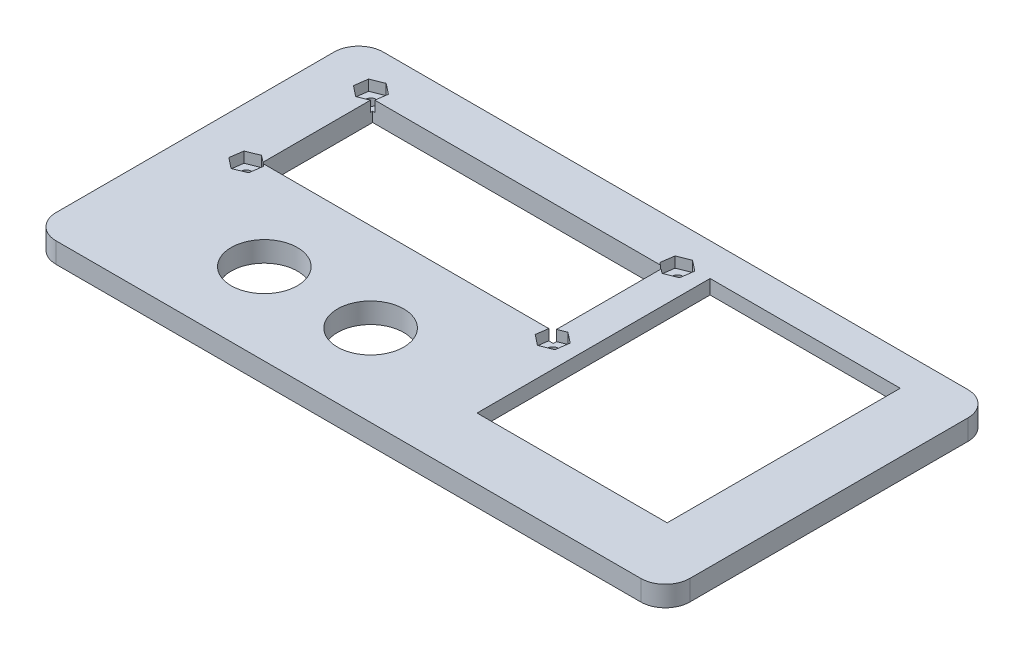
SolidWorks part; units mm, degrees
ref_plane "Front Plane" through (0, 0, 0) normal (0, 0, 1) x (1, 0, 0)
ref_plane "Top Plane" through (0, 0, 0) normal (0, 1, 0) x (1, 0, 0)
ref_plane "Right Plane" through (0, 0, 0) normal (1, 0, 0) x (0, 0, -1)
sketch "Sketch1" plane through (0, 0, 0) normal (0, 1, 0) x (1, 0, 0)
  line L1 (-77.5, -40) -> (77.5, -40)
  line L2 (-77.5, -40) -> (-77.5, 40)
  line L3 (-77.5, 40) -> (77.5, 40)
  line L4 (77.5, -40) -> (77.5, 40)
  line L5 (-77.5, -40) -> (77.5, 40) construction
  line L6 (-77.5, 40) -> (77.5, -40) construction
  point P0 (0, 0)
  dimension "D1" = 155
  dimension "D2" = 80
extrude "Boss-Extrude1" add sketch "Sketch1" along normal blind 5
sketch "Sketch2" plane through (0, 5, 0) normal (0, 1, 0) x (1, 0, 0)
  line L1 (-62.8518, 1.6691) -> (8.446, 1.6691)
  line L2 (-62.8518, 1.6691) -> (-62.8518, 28.7709)
  line L3 (-62.8518, 28.7709) -> (8.446, 28.7709)
  line L4 (8.446, 1.6691) -> (8.446, 28.7709)
  line L5 (-62.8518, 1.6691) -> (8.446, 28.7709) construction
  line L6 (-62.8518, 28.7709) -> (8.446, 1.6691) construction
  line L7 (-67.5, 15.22) -> (12.51, 15.22) construction
  line L8 (-67.5, 33) -> (12.51, 33) construction
  line L9 (-67.5, 33) -> (-67.5, -2.56) construction
  line L10 (-67.5, -2.56) -> (12.51, -2.56) construction
  line L11 (12.51, 33) -> (12.51, -2.56) construction
  line L12 (77.5, 40) -> (-77.5, 40) construction
  line L13 (-77.5, 40) -> (-77.5, -40) construction
  circle A0 centre (-64.96, -0.02) radius 1.27
  circle A1 centre (9.97, -0.02) radius 1.27
  circle A2 centre (9.97, 30.46) radius 1.27
  circle A3 centre (-64.96, 30.46) radius 1.27
  point P0 (-27.2029, 15.22)
  point P6 (-27.2029, 17.22)
  point P20 (-27.495, 15.22)
  dimension "D7" = 2.54
  dimension "D8" = 2.54
  dimension "D1" = 71.2978
  dimension "D2" = 27.1018
  dimension "D3" = 7
  dimension "D4" = 35.56
  dimension "D5" = 80.01
  dimension "D6" = 4.6482
  dimension "D9" = 33.02
  dimension "D10" = 77.47
  dimension "D11" = 5.08
  dimension "D12" = 10
extrude "Screen Cutout" cut sketch "Sketch2" against normal through all
sketch "Sketch8" plane through (0, 5, 0) normal (0, 1, 0) x (1, 0, 0)
  line L1 (-68.0135, 29.2327) -> (-65.4238, 27.202)
  line L2 (-65.4238, 27.202) -> (-62.3704, 28.4293)
  line L3 (-62.3704, 28.4293) -> (-61.9065, 31.6873)
  line L4 (-61.9065, 31.6873) -> (-64.4962, 33.718)
  line L5 (-64.4962, 33.718) -> (-67.5496, 32.4907)
  line L6 (-67.5496, 32.4907) -> (-68.0135, 29.2327)
  line L7 (6.9165, 29.2327) -> (9.5062, 27.202)
  line L8 (9.5062, 27.202) -> (12.5596, 28.4293)
  line L9 (12.5596, 28.4293) -> (13.0235, 31.6873)
  line L10 (13.0235, 31.6873) -> (10.4338, 33.718)
  line L11 (10.4338, 33.718) -> (7.3804, 32.4907)
  line L12 (7.3804, 32.4907) -> (6.9165, 29.2327)
  line L13 (6.9165, -1.2473) -> (9.5062, -3.278)
  line L14 (9.5062, -3.278) -> (12.5596, -2.0507)
  line L15 (12.5596, -2.0507) -> (13.0235, 1.2073)
  line L16 (13.0235, 1.2073) -> (10.4338, 3.238)
  line L17 (10.4338, 3.238) -> (7.3804, 2.0107)
  line L18 (7.3804, 2.0107) -> (6.9165, -1.2473)
  line L19 (-68.0135, -1.2473) -> (-65.4238, -3.278)
  line L20 (-65.4238, -3.278) -> (-62.3704, -2.0507)
  line L21 (-62.3704, -2.0507) -> (-61.9065, 1.2073)
  line L22 (-61.9065, 1.2073) -> (-64.4962, 3.238)
  line L23 (-64.4962, 3.238) -> (-67.5496, 2.0107)
  line L24 (-67.5496, 2.0107) -> (-68.0135, -1.2473)
  circle A0 centre (-64.96, 30.46) radius 2.85 construction
  circle A1 centre (9.97, 30.46) radius 2.85 construction
  circle A2 centre (9.97, -0.02) radius 2.85 construction
  circle A3 centre (-64.96, -0.02) radius 2.85 construction
  dimension "D1" = 5.7
extrude "Screen hex nuts" cut sketch "Sketch8" against normal blind 2.6
sketch "Sketch3" plane through (0, 0, 0) normal (0, 1, 0) x (1, 0, 0)
  line L0 (-40.5818, -20) -> (-14.5818, -20) construction
  line L1 (-48.7318, -11.45) -> (-48.7318, -28.55) construction
  line L2 (-48.7318, -28.55) -> (-6.4318, -28.55) construction
  line L3 (-62.4954, 1.6691) -> (7.3317, 1.6691) construction
  line L4 (-77.5, -40) -> (77.5, -40) construction
  line L7 (-27.5818, 26.9252) -> (-27.5818, -22.8987) construction
  circle A0 centre (-40.5818, -20) radius 8.1
  circle A1 centre (-14.5818, -20) radius 8.1
  circle A2 centre (-48.7318, -11.45) radius 1.1906
  circle A3 centre (-6.4318, -11.45) radius 1.1906
  circle A4 centre (-6.4318, -28.55) radius 1.1906
  circle A5 centre (-48.7318, -28.55) radius 1.1906
  point P4 (-27.5818, -28.55)
  point P14 (-27.5818, -20)
  point P19 (-27.5818, 1.6691)
  dimension "D1" = 16.2
  dimension "D2" = 26
  dimension "D3" = 2.3813
  dimension "D4" = 17.1
  dimension "D5" = 20
  dimension "D6" = 42.3
  dimension "D7" = 8.55
extrude "Ultrasound Cutouts" cut sketch "Sketch3" along normal through all contours A1 | A0
extrude "Cut-Extrude2" cut sketch "Sketch3<3>" along normal blind 3.175
sketch "Sketch3<3>" plane through (0, 0, 0) normal (0, 1, 0) x (1, 0, 0) same geometry as "Sketch3"
sketch "Sketch4" plane through (0, 5, 0) normal (0, 1, 0) x (1, 0, 0)
  circle A0 centre (-21.6513, -28.8183) radius 0.85
  circle A1 centre (20.3487, -11.8183) radius 0.85
  circle A2 centre (-21.6513, -11.8183) radius 0.85
  circle A3 centre (20.3487, -28.8183) radius 0.85
  dimension "D1" = 1.7
  dimension "D2" = 17
  dimension "D3" = 42
extrude "Ultrasound Bolt Holes" [suppressed] cut sketch "Sketch4" against normal through all
sketch "Sketch5" plane through (0, 0, 0) normal (0, -1, 0) x (1, 0, 0)
  line L0 (-6.322, 30.05) -> (-48.622, 30.05) construction
  line L1 (-21.472, 30.05) -> (-33.472, 30.05)
  line L2 (-21.472, 30.05) -> (-21.472, 25.05)
  line L3 (-21.472, 25.05) -> (-33.472, 25.05)
  line L4 (-33.472, 30.05) -> (-33.472, 25.05)
  line L5 (-21.472, 30.05) -> (-33.472, 25.05) construction
  line L6 (-21.472, 25.05) -> (-33.472, 30.05) construction
  circle A1 centre (-6.4318, 28.55) radius 1.1906 construction
  point P0 (-27.472, 27.55)
  point P13 (-27.472, 30.05)
  point P14 (-27.472, 30.05)
  dimension "D3" = 1.5
  dimension "D1" = 12
  dimension "D2" = 5
extrude "US Clock cutout" cut sketch "Sketch5" against normal blind 4
sketch "Sketch6" plane through (0, 0, 0) normal (0, -1, 0) x (1, 0, 0)
  line L0 (-21.472, 27.55) -> (-33.472, 27.55) construction
  line L1 (-22.472, 13.3) -> (-32.472, 13.3)
  line L2 (-22.472, 13.3) -> (-22.472, 9.8)
  line L3 (-22.472, 9.8) -> (-32.472, 9.8)
  line L4 (-32.472, 13.3) -> (-32.472, 9.8)
  line L5 (-22.472, 13.3) -> (-32.472, 9.8) construction
  line L6 (-22.472, 9.8) -> (-32.472, 13.3) construction
  line L7 (-21.472, 25.05) -> (-21.472, 30.05) construction
  line L8 (-33.472, 30.05) -> (-33.472, 25.05) construction
  line L9 (-6.6073, 10.2724) -> (-48.9073, 10.2724) construction
  line L10 (-27.472, 5.8213) -> (-27.472, 1.0358) construction
  point P0 (-27.472, 11.55)
  point P19 (0, 0)
  point P20 (-27.472, 27.55)
  dimension "D1" = 10
  dimension "D2" = 3.5
  dimension "D3" = 16
extrude "US Pin cutout" cut sketch "Sketch6" against normal blind 2
fillet "Fillet2" [suppressed] radius 1
ref_plane "Magnet plane" through (0, 0.2, 0) normal (0, -1, 0) x (-1, 0, 0)
sketch "Sketch9" plane through (0, 0.2, 0) normal (0, -1, 0) x (-1, 0, 0)
  line L0 (-77.5, -40) -> (-77.5, 40) construction
  line L1 (-77.5, 40) -> (77.5, 40) construction
  line L2 (77.5, -40) -> (-77.5, -40) construction
  line L3 (77.5, 40) -> (77.5, -40) construction
  circle A0 centre (-71.5, 34) radius 3.15
  circle A1 centre (71.5, 34) radius 3.15
  circle A2 centre (-71.5, -34) radius 3.15
  circle A3 centre (71.5, -34) radius 3.15
  dimension "D1" = 6.3
  dimension "D2" = 6
  dimension "D3" = 6
  dimension "D4" = 6
  dimension "D5" = 6
extrude "Magnet Holes" cut sketch "Sketch9" against normal blind 2.1
fillet "Fillet1" radius 6 4 edges at (77.5, 2.5, -40) (77.5, 2.5, 40) (-77.5, 2.5, 40) (-77.5, 2.5, -40)
sketch "Sketch10" plane through (0, 5, 0) normal (0, 1, 0) x (1, 0, 0)
  line L0 (8.446, 2.439) -> (8.446, 28.0333) construction
  line L1 (16.446, -25) -> (62.946, -25)
  line L2 (16.446, -25) -> (16.446, 32)
  line L3 (16.446, 32) -> (62.946, 32)
  line L4 (62.946, -25) -> (62.946, 32)
  line L5 (16.446, -25) -> (62.946, 32) construction
  line L6 (16.446, 32) -> (62.946, -25) construction
  line L7 (71.5, 40) -> (-71.5, 40) construction
  point P0 (39.696, 3.5)
  dimension "D1" = 46.5
  dimension "D2" = 57
  dimension "D3" = 8
  dimension "D4" = 8
extrude "Keypad cutout" cut sketch "Sketch10" against normal through all
sketch "Sketch11" plane through (0, 0, 0) normal (0, -1, 0) x (1, 0, 0)
  line L0 (58.696, 34.5) -> (58.696, 28.5)
  line L1 (65.696, -35.5) -> (13.696, -35.5)
  line L2 (65.696, -35.5) -> (65.696, 28.5)
  line L3 (65.696, 28.5) -> (13.696, 28.5)
  line L4 (13.696, -35.5) -> (13.696, 28.5)
  line L5 (58.696, 34.5) -> (20.696, 34.5)
  line L6 (58.696, 28.5) -> (20.696, 28.5)
  line L7 (20.696, 34.5) -> (20.696, 28.5)
  line L8 (58.696, 34.5) -> (20.696, 28.5) construction
  line L9 (58.696, 28.5) -> (20.696, 34.5) construction
  line L10 (62.946, -32) -> (16.446, 25) construction
  line L11 (16.446, -32) -> (62.946, 25) construction
  line L12 (39.696, 25.3529) -> (39.696, -31.6471) construction
  line L14 (62.946, -3.5) -> (16.446, -3.5) construction
  point P4 (39.696, 28.5)
  point P5 (39.696, 31.5)
  point P6 (39.696, 28.5)
  point P16 (39.696, -35.5)
  point P23 (65.696, -3.5)
  point P24 (39.696, -3.5)
  line M12 (62.946, 25) -> (62.946, -32)
  line M13 (62.946, -32) -> (16.446, -32)
  line M14 (16.446, -32) -> (16.446, 25)
  line M15 (16.446, 25) -> (62.946, 25)
  dimension "D1" = 52
  dimension "D2" = 64
  dimension "D3" = 38
  dimension "D4" = 6
extrude "Cut-Extrude1" cut sketch "Sketch11" against normal blind 1.5 contours M12 M15 M14 M13 | L4 L1 L2 L3 M15 M12 M13 M14 | L5 L7 L3 L0 region at (39.696, 0, 31.5) region at (62.196, 0, 27.6754) region at (39.696, 0, -3.5)
